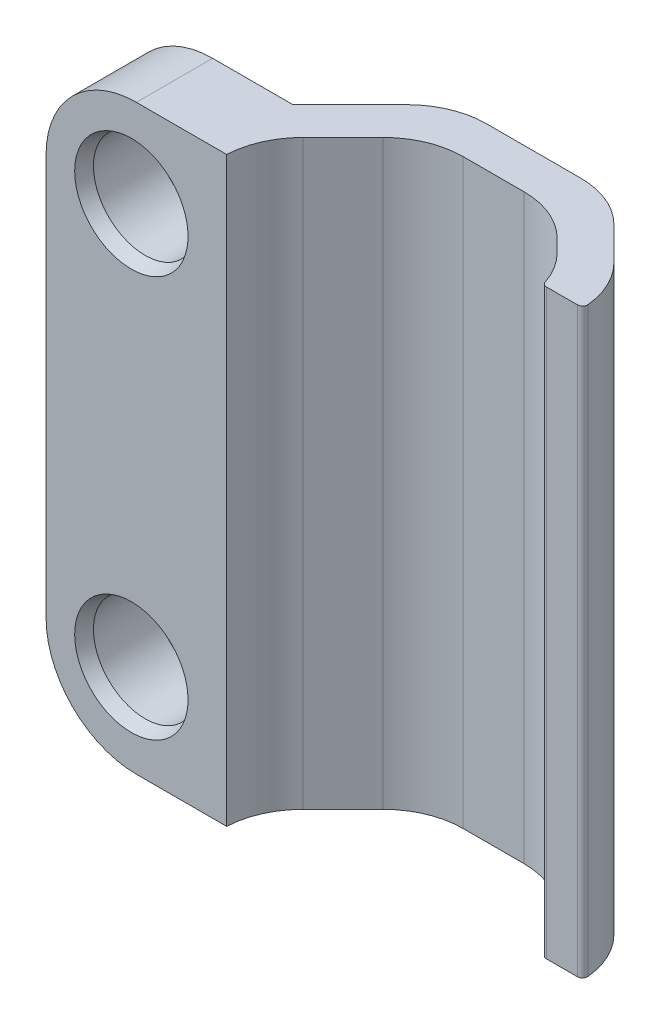
SolidWorks part; units mm, degrees
material "PBT General Purpose"
ref_plane "Front Plane" through (0, 0, 0) normal (0, 0, 1) x (1, 0, 0)
ref_plane "Top Plane" through (0, 0, 0) normal (0, 1, 0) x (1, 0, 0)
ref_plane "Right Plane" through (0, 0, 0) normal (1, 0, 0) x (0, 0, -1)
sketch "Sketch1" plane through (0, 0, 0) normal (0, 1, 0) x (1, 0, 0)
  line L0 (0, 0) -> (0, 3.8)
  line L1 (0, 3.8) -> (8.5, 3.8)
  line L2 (0, 0) -> (9, 0)
  line L3 (9, 0) -> (9, 1.4716)
  line L4 (4.5, 0) -> (4.5, 3.8) construction
  line L5 (2, 3.8) -> (2, 0) construction
  line L6 (7, 3.8) -> (7, 0) construction
  line L7 (2, 1.9) -> (7, 1.9) construction
  line L8 (8.5, 3.8) -> (12.5, 7.8)
  line L9 (12.5, 7.8) -> (20.5, 7.8)
  line L10 (20.5, 7.8) -> (24.5, 3.8)
  line L12 (22.5, 2.9716) -> (19.6716, 5.8)
  line L13 (19.6716, 5.8) -> (13.3284, 5.8)
  line L14 (13.3284, 5.8) -> (9, 1.4716)
  line L15 (11.9142, 4.3858) -> (10.5, 5.8) construction
  line L16 (16.5, 5.8) -> (16.5, 7.8) construction
  line L17 (21.0858, 4.3858) -> (22.5, 5.8) construction
  line L18 (4.5, 0) -> (24.5, 0) construction
  line L19 (22.5, 2.9716) -> (22.5, 2.25)
  line L20 (22.5, 2.25) -> (24.5, 2.25)
  line L21 (24.5, 2.25) -> (24.5, 3.8)
  point P14 (4.5, 1.9)
  point P29 (21.7184, 3.8)
  point P35 (10.5, 5.8)
  dimension "D1" = 3.8
  dimension "D2" = 9
  dimension "D3" = 5
  dimension "D4" = 4
  dimension "D5" = 2
  dimension "D6" = 20
  dimension "D7" = 4
  dimension "D8" = 135
  dimension "D9" = 135
  dimension "D10" = 2.25
extrude "Boss-Extrude1" add sketch "Sketch1" along normal blind 29
sketch "Sketch2" plane through (0, 0, -3.8) normal (0, 0, -1) x (-1, 0, 0)
  line L0 (0, 14.5) -> (-8.5, 14.5) construction
  line L3 (0, 29) -> (0, 0) construction
  line L4 (-8.5, 29) -> (-8.5, 0) construction
  line L5 (-4.25, 4.5) -> (-4.25, 24.5) construction
  circle A0 centre (-4.25, 4.5) radius 2.575
  circle A1 centre (-4.25, 24.5) radius 2.575
  point P8 (-4.25, 14.5)
  point P11 (-4.25, 3.4538)
  dimension "D1" = 5.15
  dimension "D2" = 20
extrude "Cut-Extrude1" cut sketch "Sketch2" against normal through all both and the other way through all
fillet "Fillet1" radius 4.5 2 edges at (0, 0, -1.9) (0, 29, -1.9)
fillet "Fillet2" radius 4 7 edges at (9, 14.5, -1.4716) (19.6716, 14.5, -5.8) (13.3284, 14.5, -5.8) (20.5, 14.5, -7.8) (12.5, 14.5, -7.8) (24.5, 14.5, -3.8) (22.5, 14.5, -2.9716)
chamfer "Chamfer1" distance 0.25 angle 70 2 edges at (1.675, 24.5, 0) (1.675, 4.5, 0) first distance on face at (1.675, 4.5, 0)
fillet "Fillet4" radius 0.25 2 edges at (22.5, 14.5, -2.25) (24.5, 14.5, -2.25)
